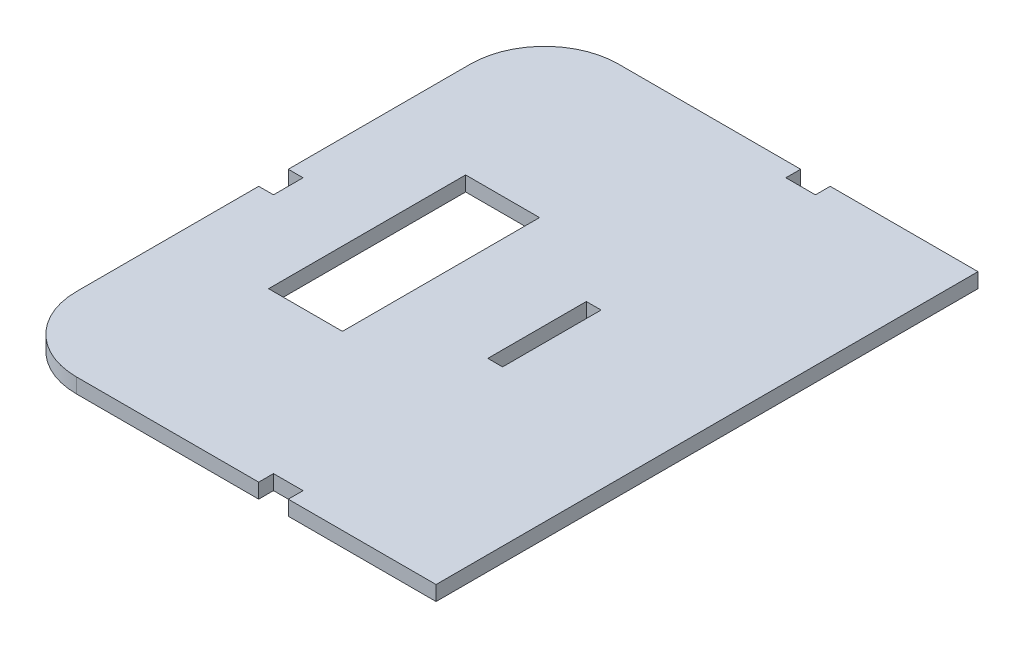
SolidWorks part; units mm, degrees
ref_plane "Спереди" through (0, 0, 0) normal (0, 0, 1) x (1, 0, 0)
ref_plane "Сверху" through (0, 0, 0) normal (0, 1, 0) x (1, 0, 0)
ref_plane "Справа" through (0, 0, 0) normal (1, 0, 0) x (0, 0, -1)
other "Configuration Table"
sketch "Эскиз4" plane through (0, 0, 0) normal (0, 1, 0) x (1, 0, 0)
  line L0 (88, 110) -> (88, 0)
  line L1 (0, 0) -> (52, 0)
  line L2 (0, 0) -> (0, 52)
  line L3 (0, 110) -> (52, 110)
  line L5 (58, 0) -> (88, 0)
  line L6 (55, 107) -> (52, 107)
  line L7 (52, 107) -> (55, 107)
  line L8 (55, 107) -> (58, 107)
  line L9 (52, 107) -> (52, 110)
  line L10 (58, 107) -> (58, 110)
  line L11 (58, 3) -> (58, 0)
  line L12 (55, 3) -> (58, 3)
  line L13 (55, 3) -> (52, 3)
  line L14 (52, 3) -> (52, 0)
  line L15 (3, 55) -> (3, 58)
  line L16 (3, 55) -> (3, 52)
  line L17 (3, 58) -> (0, 58)
  line L18 (3, 52) -> (0, 52)
  line L19 (55, 107) -> (55, 3) construction
  line L20 (3, 55) -> (55, 55) construction
  line L22 (0, 58) -> (0, 110)
  line L23 (58, 110) -> (88, 110)
  point P1 (58, 108.5)
  dimension "D1" = 55
  dimension "D2" = 110
  dimension "D3" = 3
  dimension "D4" = 3
  dimension "D5" = 6
  dimension "D6" = 3
  dimension "D7" = 3
  dimension "D8" = 3
  dimension "D9" = 3
  dimension "D10" = 3
  dimension "D11" = 3
  dimension "D12" = 3
  dimension "D13" = 30
extrude "Бобышка-Вытянуть3" add sketch "Эскиз4" along normal blind 3 contours L3 L10 L8 L6 L9 L2 L17 L15 L16 L18 L1 L14 L13 L12 L11 region at (44.0383, 0, -55)
sketch "Sketch1" plane through (0, 3, 0) normal (0, 1, 0) x (1, 0, 0)
  line L0 (3, 52) -> (3, 58) construction
  line L13 (3, 55) -> (107, 55) construction
  line L15 (55, 107) -> (55, 3) construction
  line L16 (52, 107) -> (58, 107) construction
  line L19 (19, 75) -> (34, 75)
  line L20 (19, 75) -> (19, 35)
  line L21 (19, 35) -> (34, 35)
  line L22 (34, 75) -> (34, 35)
  line L23 (53.5, 65) -> (56.5, 65)
  line L24 (53.5, 65) -> (53.5, 45)
  line L25 (53.5, 45) -> (56.5, 45)
  line L26 (56.5, 65) -> (56.5, 45)
  dimension "D1" = 3
  dimension "D2" = 20
  dimension "D3" = 16
  dimension "D4" = 15
  dimension "D5" = 40
extrude "Cut-Extrude1" cut sketch "Sketch1" against normal blind 10
fillet "Fillet1" radius 15 2 edges at (0, 1.5, 0) (0, 1.5, -110)
